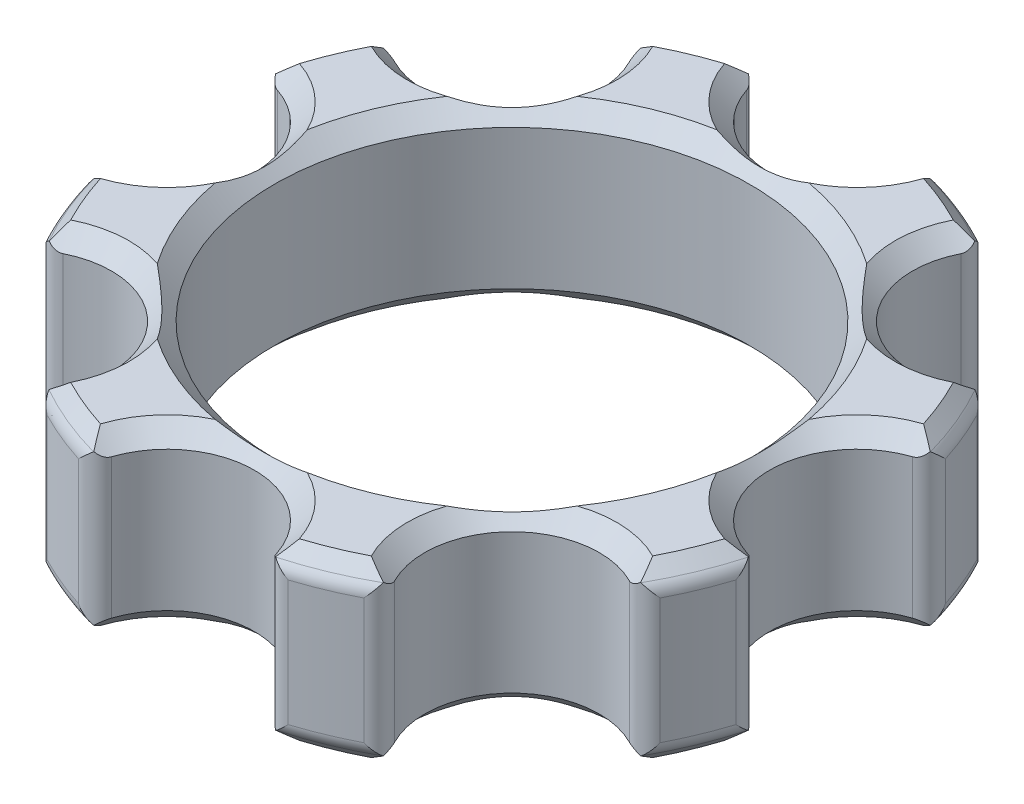
SolidWorks part; units mm, degrees
material "ABS"
ref_plane "Front Plane" through (0, 0, 0) normal (0, 0, 1) x (1, 0, 0)
ref_plane "Top Plane" through (0, 0, 0) normal (0, 1, 0) x (1, 0, 0)
ref_plane "Right Plane" through (0, 0, 0) normal (1, 0, 0) x (0, 0, -1)
sketch "Çizim1" plane through (0, 0, 0) normal (0, 1, 0) x (1, 0, 0)
  circle A0 centre (0, 0) radius 13.6
  circle A1 centre (0, 0) radius 19.75
  circle A2 centre (0, 19.75) radius 5
  circle A6 centre (13.9654, 13.9654) radius 5
  circle A7 centre (19.75, 0) radius 5
  circle A8 centre (13.9654, -13.9654) radius 5
  circle A9 centre (0, -19.75) radius 5
  circle A10 centre (-13.9654, -13.9654) radius 5
  circle A11 centre (-19.75, 0) radius 5
  circle A12 centre (-13.9654, 13.9654) radius 5
  point P22 (0, 0)
  dimension "D1" = 10
  dimension "D2" = 27.2
  dimension "D3" = 39.5
  dimension "D4" = 8
extrude "Yükseklik-Ekstrüzyon1" add sketch "Çizim1" along normal blind 10 contours A7 A1 A6 A2 A0 region at (14.2093, 0, 0)
chamfer "Pah1" distance 1 angle 45 34 edges at (0, 0, 13.6) (-18.2466, 0, -7.558) (-14.75, 0, 0) (-18.2466, 0, 7.558) (-10.4298, 0, 10.4298) (-7.558, 0, 18.2466) (0, 0, 14.75) (7.558, 0, 18.2466) (10.4298, 0, 10.4298) (18.2466, 0, 7.558) (14.75, 0, 0) (18.2466, 0, -7.558) (10.4298, 0, -10.4298) (7.558, 0, -18.2466) (0, 0, -14.75) (-7.558, 0, -18.2466) (-10.4298, 0, -10.4298) (0, 10, 13.6) (-7.558, 10, -18.2466) (0, 10, -14.75) (7.558, 10, -18.2466) (10.4298, 10, -10.4298) (18.2466, 10, -7.558) (14.75, 10, 0) (18.2466, 10, 7.558) (10.4298, 10, 10.4298) (7.558, 10, 18.2466) (0, 10, 14.75) (-7.558, 10, 18.2466) (-10.4298, 10, 10.4298) (-18.2466, 10, 7.558) (-14.75, 10, 0) (-18.2466, 10, -7.558) (-10.4298, 10, -10.4298)
fillet "Radyus1" radius 1 32 edges at (18.2466, 9, 7.558) (19.1171, 5, 4.9598) (18.2466, 1, 7.558) (17.0249, 5, 10.0107) (7.558, 9, 18.2466) (10.0107, 5, 17.0249) (7.558, 1, 18.2466) (4.9598, 5, 19.1171) (-7.558, 9, 18.2466) (-4.9598, 5, 19.1171) (-7.558, 1, 18.2466) (-10.0107, 5, 17.0249) (-18.2466, 9, 7.558) (-17.0249, 5, 10.0107) (-18.2466, 1, 7.558) (-19.1171, 5, 4.9598) (-18.2466, 9, -7.558) (-19.1171, 5, -4.9598) (-18.2466, 1, -7.558) (-17.0249, 5, -10.0107) (-7.558, 9, -18.2466) (-10.0107, 5, -17.0249) (-7.558, 1, -18.2466) (-4.9598, 5, -19.1171) (7.558, 9, -18.2466) (4.9598, 5, -19.1171) (7.558, 1, -18.2466) (10.0107, 5, -17.0249) (18.2466, 9, -7.558) (17.0249, 5, -10.0107) (18.2466, 1, -7.558) (19.1171, 5, -4.9598)
